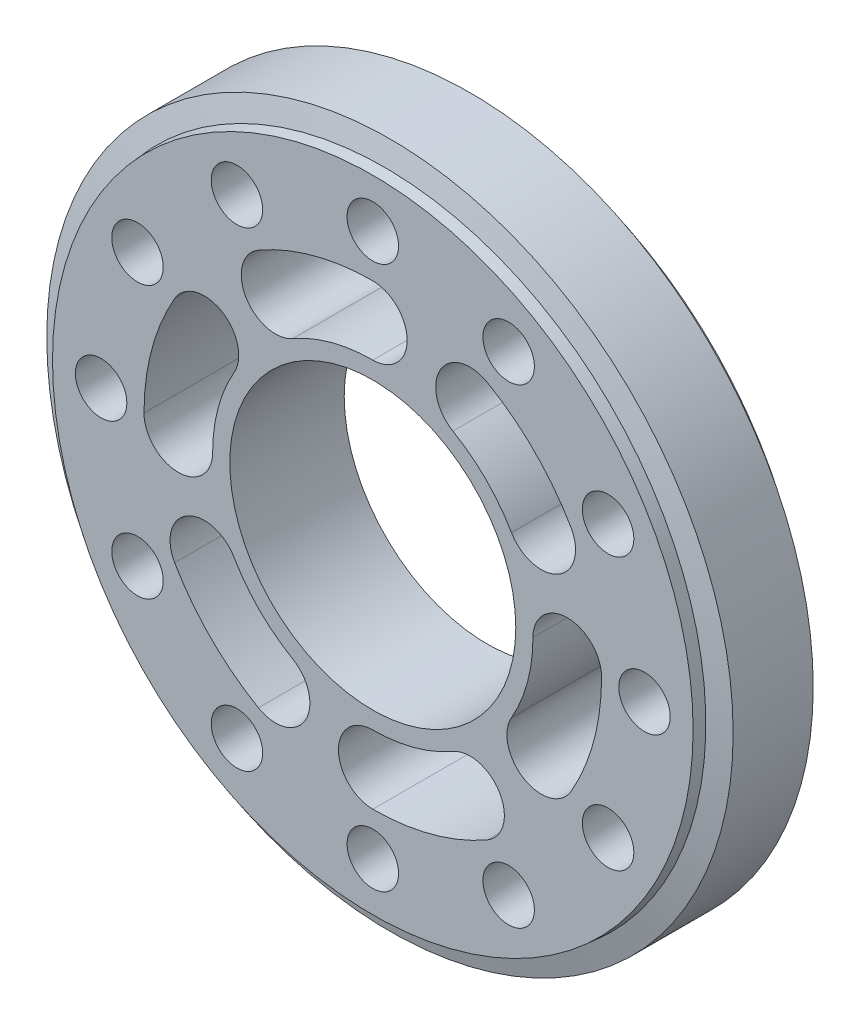
SolidWorks part; units mm, degrees
ref_plane "Front Plane" through (0, 0, 0) normal (0, 0, 1) x (1, 0, 0)
ref_plane "Top Plane" through (0, 0, 0) normal (0, 1, 0) x (1, 0, 0)
ref_plane "Right Plane" through (0, 0, 0) normal (1, 0, 0) x (0, 0, -1)
sketch "Sketch1" plane through (0, 0, 0) normal (1, 0, 0) x (0, 0, -1)
  line L0 (0, 0) -> (0, 30)
  line L1 (0, 30) -> (4, 30)
  line L2 (4, 30) -> (4, 28)
  line L3 (4, 28) -> (5, 28)
  line L4 (5, 28) -> (5, 0)
  line L5 (5, 0) -> (0, 0)
  line L6 (0, 0) -> (-18.747, 0) construction
  dimension "D1" = 56
  dimension "D2" = 60
  dimension "D3" = 1
  dimension "D4" = 4
revolve "Revolve1" add sketch "Sketch1" angle 360 about L6
mirror "Mirror1" about plane through (0, 0, 0) normal (0, 0, 1) of bodies 101
sketch "Sketch2" plane through (0, 0, 5) normal (0, 0, 1) x (1, 0, 0)
  line L0 (0, 0) -> (11.875, 20.5681) construction
  line L1 (4.5033, 23.75) -> (2.2517, 27.65)
  line L2 (2.2517, 27.65) -> (-2.2517, 27.65)
  line L3 (-2.2517, 27.65) -> (-4.5033, 23.75)
  line L4 (-4.5033, 23.75) -> (-2.2517, 19.85)
  line L5 (-2.2517, 19.85) -> (2.2517, 19.85)
  line L6 (2.2517, 19.85) -> (4.5033, 23.75)
  line L7 (0, 0) -> (0, 23.75) construction
  line L8 (18.3164, 15.775) -> (16.0648, 11.875)
  line L9 (22.8198, 15.775) -> (18.3164, 15.775)
  line L10 (25.0714, 11.875) -> (22.8198, 15.775)
  line L11 (22.8198, 7.975) -> (25.0714, 11.875)
  line L12 (18.3164, 7.975) -> (22.8198, 7.975)
  line L13 (16.0648, 11.875) -> (18.3164, 7.975)
  line L14 (0, 0) -> (20.5681, 11.875) construction
  line L15 (0, 0) -> (23.75, 0) construction
  line L16 (22.8198, -7.975) -> (18.3164, -7.975)
  line L17 (25.0714, -11.875) -> (22.8198, -7.975)
  line L18 (22.8198, -15.775) -> (25.0714, -11.875)
  line L19 (18.3164, -15.775) -> (22.8198, -15.775)
  line L20 (16.0648, -11.875) -> (18.3164, -15.775)
  line L21 (18.3164, -7.975) -> (16.0648, -11.875)
  line L22 (0, 0) -> (20.5681, -11.875) construction
  line L23 (0, 0) -> (11.875, -20.5681) construction
  line L24 (4.5033, -23.75) -> (2.2517, -19.85)
  line L25 (2.2517, -27.65) -> (4.5033, -23.75)
  line L26 (-2.2517, -27.65) -> (2.2517, -27.65)
  line L27 (-4.5033, -23.75) -> (-2.2517, -27.65)
  line L28 (-2.2517, -19.85) -> (-4.5033, -23.75)
  line L29 (2.2517, -19.85) -> (-2.2517, -19.85)
  line L30 (0, 0) -> (0, -23.75) construction
  line L31 (0, 0) -> (-11.875, -20.5681) construction
  line L32 (-18.3164, -15.775) -> (-16.0648, -11.875)
  line L33 (-22.8198, -15.775) -> (-18.3164, -15.775)
  line L34 (-25.0714, -11.875) -> (-22.8198, -15.775)
  line L35 (-22.8198, -7.975) -> (-25.0714, -11.875)
  line L36 (-18.3164, -7.975) -> (-22.8198, -7.975)
  line L37 (-16.0648, -11.875) -> (-18.3164, -7.975)
  line L38 (0, 0) -> (-20.5681, -11.875) construction
  line L39 (0, 0) -> (-23.75, 0) construction
  line L40 (-22.8198, 7.975) -> (-18.3164, 7.975)
  line L41 (-25.0714, 11.875) -> (-22.8198, 7.975)
  line L42 (-22.8198, 15.775) -> (-25.0714, 11.875)
  line L43 (-18.3164, 15.775) -> (-22.8198, 15.775)
  line L44 (-16.0648, 11.875) -> (-18.3164, 15.775)
  line L45 (-18.3164, 7.975) -> (-16.0648, 11.875)
  line L46 (0, 0) -> (-20.5681, 11.875) construction
  line L47 (0, 0) -> (-11.875, 20.5681) construction
  circle A0 centre (0, 0) radius 23.75 construction
  circle A1 centre (0, 23.75) radius 2.25
  circle A2 centre (0, 23.75) radius 3.9 construction
  circle A3 centre (11.875, 20.5681) radius 2.25
  circle A4 centre (11.875, 20.5681) radius 3.9
  circle A5 centre (23.75, 0) radius 3.9
  circle A6 centre (23.75, 0) radius 2.25
  circle A7 centre (20.5681, 11.875) radius 2.25
  circle A8 centre (20.5681, 11.875) radius 3.9 construction
  circle A9 centre (11.875, -20.5681) radius 3.9
  circle A10 centre (11.875, -20.5681) radius 2.25
  circle A11 centre (20.5681, -11.875) radius 2.25
  circle A12 centre (20.5681, -11.875) radius 3.9 construction
  circle A13 centre (-11.875, -20.5681) radius 3.9
  circle A14 centre (-11.875, -20.5681) radius 2.25
  circle A15 centre (0, -23.75) radius 2.25
  circle A16 centre (0, -23.75) radius 3.9 construction
  circle A17 centre (-23.75, 0) radius 3.9
  circle A18 centre (-23.75, 0) radius 2.25
  circle A19 centre (-20.5681, -11.875) radius 2.25
  circle A20 centre (-20.5681, -11.875) radius 3.9 construction
  circle A21 centre (-11.875, 20.5681) radius 3.9
  circle A22 centre (-11.875, 20.5681) radius 2.25
  circle A23 centre (-20.5681, 11.875) radius 2.25
  circle A24 centre (-20.5681, 11.875) radius 3.9 construction
  circle A25 centre (0, 0) radius 12.5
  point P74 (0, 0)
  point P78 (0, 0)
  dimension "D1" = 47.5
  dimension "D2" = 4.5
  dimension "D3" = 7.8
  dimension "D5" = 4.5
  dimension "D6" = 7.8
  dimension "D8" = 25
  dimension "D4" = 30
  dimension "D7" = 6
extrude "Cut-Extrude1" cut sketch "Sketch2" against normal blind 12 contours A1 | A22 | A23 | A18 | A19 | A14 | A15 | A10 | A11 | A7 | A3 | A25 | A6 region at (0, 23.75, 5) region at (11.875, 20.5681, 5) region at (20.5681, 11.875, 5) region at (11.875, -20.5681, 5) region at (20.5681, -11.875, 5) region at (-11.875, -20.5681, 5) region at (0, -23.75, 5) region at (-23.75, 0, 5) region at (-20.5681, -11.875, 5) region at (-11.875, 20.5681, 5) region at (-20.5681, 11.875, 5) region at (0, 0, 5)
chamfer "Chamfer1" distance 2 distance2 0.5 1 edges at (-30, 0, 4) first distance on face at (-30, 0, 4)
chamfer "Chamfer2" distance 0.5 distance2 2 1 edges at (-30, 0, -4) first distance on face at (30, 0, 3.5)
sketch "Sketch3" plane through (0, 0, -5) normal (0, 0, -1) x (-1, 0, 0)
  line L0 (0, 0) -> (0, 17) construction
  line L1 (0, 0) -> (8.5, 14.7224) construction
  arc A0 (0, 17) -> (8.5, 14.7224) centre (0, 0) cw construction
  arc A1 (10, 17.3205) -> (0, 20) centre (0, 0) ccw
  arc A2 (7, 12.1244) -> (0, 14) centre (0, 0) ccw
  arc A3 (7, 12.1244) -> (10, 17.3205) centre (8.5, 14.7224) ccw
  arc A4 (0, 20) -> (0, 14) centre (0, 17) ccw
  point P4 (4.3999, 16.4207)
  dimension "D1" = 17
  dimension "D2" = 3
  dimension "D3" = 30
extrude "Cut-Extrude2" cut sketch "Sketch3" against normal blind 20
pattern_circular "CirPattern1" count 6 over 360 about axis through (0, 0, -7) along (0, 0, 1) of "Cut-Extrude2" reverse direction yes
draft "Draft1" type of draft neutral plane draft angle 5 faces to draft 1 face at (-28, 0, 4) neutral plane through (0, 28, 5) neutral plane normal (0, 0, 1) parameters "D1"=5
draft "Draft2" type of draft neutral plane draft angle 5 faces to draft 1 face at (-28, 0, -4) neutral plane through (0, 28, -5) neutral plane normal (0, 0, -1) parameters "D1"=5
